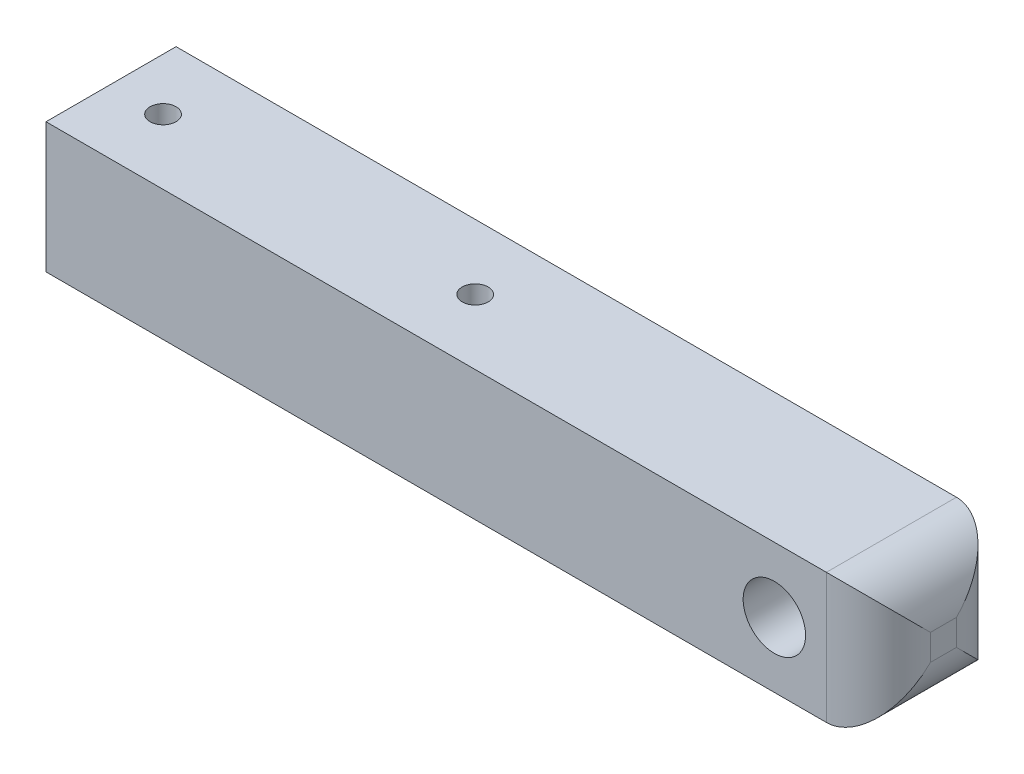
SolidWorks part; units mm, degrees
material "ABS"
ref_plane "Front Plane" through (0, 0, 0) normal (0, 0, 1) x (1, 0, 0)
ref_plane "Top Plane" through (0, 0, 0) normal (0, 1, 0) x (1, 0, 0)
ref_plane "Right Plane" through (0, 0, 0) normal (1, 0, 0) x (0, 0, -1)
sketch "Sketch1" plane through (0, 0, 0) normal (0, 0, 1) x (1, 0, 0)
  line L0 (0, 0) -> (101.6, 0)
  line L1 (101.6, 0) -> (101.6, 31.75)
  line L2 (101.6, 31.75) -> (-101.6, 31.75)
  line L3 (-101.6, 31.75) -> (-101.6, 0)
  line L4 (-101.6, 0) -> (0, 0)
  dimension "D1" = 31.75
  dimension "D2" = 203.2
extrude "Boss-Extrude1" add sketch "Sketch1" along normal mid plane 31.75
sketch "Sketch2" plane through (-101.6, 0, 0) normal (-1, 0, 0) x (0, 0, 1)
  line L0 (0, 4.9711) -> (-8.9803, 13.9513)
  line L1 (-8.9803, 13.9513) -> (-9.8783, 13.0533)
  line L2 (-9.8783, 13.0533) -> (0, 3.175)
  line L3 (0, 3.175) -> (9.8783, 13.0533)
  line L4 (9.8783, 13.0533) -> (8.9803, 13.9513)
  line L5 (8.9803, 13.9513) -> (0, 4.9711)
  line L6 (-11.3146, 0) -> (21.0706, 0) construction
  line L7 (-15.875, 31.75) -> (-15.875, 0) construction
  line L8 (-9.8783, 13.0533) -> (-15.875, 13.0533) construction
  line L9 (9.8783, 13.0533) -> (15.875, 13.0533) construction
  line L10 (15.875, 31.75) -> (15.875, 0) construction
  dimension "D1" = 1.27
  dimension "D2" = 3.175
  dimension "D3" = 12.7
extrude "Cut-Extrude1" cut sketch "Sketch2" against normal blind 152.4
hole_wizard "1/2 (0.5) Diameter Hole1" positions "Sketch3" profile "Sketch4" hole size "1/2" standard "ANSI Inch" end condition through all
sketch "Sketch3" plane through (0, 0, 15.875) normal (0, 0, 1) x (1, 0, 0)
  line L0 (-101.6, 31.75) -> (-101.6, 0) construction
  line L1 (-101.6, 15.875) -> (162.3719, 15.875) construction
  point P0 (76.2, 15.875)
  dimension "D1" = 177.8
sketch "Sketch4" plane through (76.2, 15.875, 15.875) normal (1, 0, 0) x (0, -1, 0)
  line L0 (0, 0) -> (0, 31.75)
  line L1 (0, 31.75) -> (7.62, 31.75)
  line L2 (7.62, 31.75) -> (7.62, 0)
  line L5 (7.62, 0) -> (0, 0)
  line L11 (0, -6.35) -> (0, 107.95) construction
  dimension "Thru Hole Dia." = 15.24
  dimension "Thru Hole Depth" = 31.75
hole_wizard "1/4 (0.25) Diameter Hole1" positions "Sketch5" profile "Sketch6" hole size "1/4" standard "ANSI Inch" end condition through all
sketch "Sketch5" plane through (0, 31.75, 0) normal (0, 1, 0) x (1, 0, 0)
  line L0 (-101.6, -15.875) -> (-101.6, 15.875) construction
  point P0 (-88.9, 0)
  point P2 (-12.7, 0)
  dimension "D1" = 12.7
  dimension "D2" = 76.2
sketch "Sketch6" plane through (-88.9, 31.75, 0) normal (1, 0, 0) x (0, 0, 1)
  line L0 (0, 0) -> (0, 31.75)
  line L1 (0, 31.75) -> (3.175, 31.75)
  line L2 (3.175, 31.75) -> (3.175, 0)
  line L5 (3.175, 0) -> (0, 0)
  line L11 (0, -6.35) -> (0, 107.95) construction
  dimension "Thru Hole Dia." = 6.35
  dimension "Thru Hole Depth" = 31.75
fillet "Fillet1" radius 12.7 4 edges at (101.6, 0, 0) (101.6, 15.875, -15.875) (101.6, 31.75, 0) (101.6, 15.875, 15.875)
